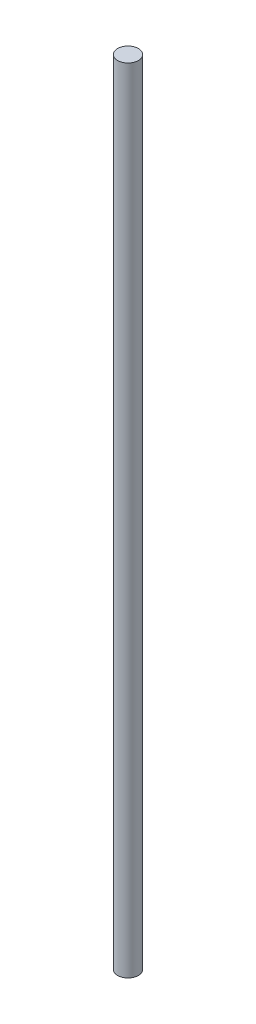
SolidWorks part; units mm, degrees
ref_plane "Front Plane" through (0, 0, 0) normal (0, 0, 1) x (1, 0, 0)
ref_plane "Top Plane" through (0, 0, 0) normal (0, 1, 0) x (1, 0, 0)
ref_plane "Right Plane" through (0, 0, 0) normal (1, 0, 0) x (0, 0, -1)
sketch "Sketch1" plane through (0, 0, 0) normal (0, 1, 0) x (1, 0, 0)
  circle A0 centre (0, 0) radius 2.5
  dimension "D1" = 5
extrude "Boss-Extrude1" add sketch "Sketch1" along normal offset from surface (190 mm away) 10 offset beyond the face yes
